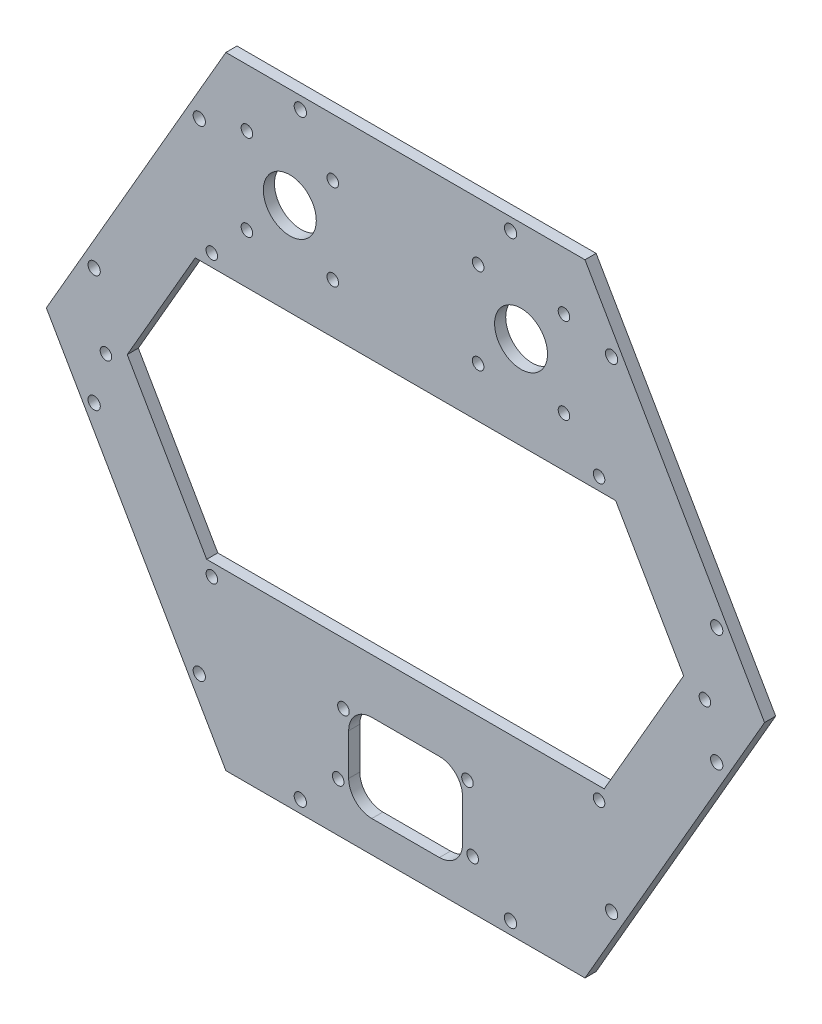
SolidWorks part; units mm, degrees
note: '?' marks a value the reader was unsure of. The reader was unsure of these and kept them because the rebuilt part matched: thickness of "Flange-base1", "Chapa metálica1", "Chapa metálica2", "Chapa metálica3", "Chapa metálica4", "Chapa metálica5", "Chapa metálica6", "Chapa metálica7", "Chapa metálica8".
ref_plane "Plano frontal" through (0, 0, 0) normal (0, 0, 1) x (1, 0, 0)
ref_plane "Plano superior" through (0, 0, 0) normal (0, 1, 0) x (1, 0, 0)
ref_plane "Plano direito" through (0, 0, 0) normal (1, 0, 0) x (0, 0, -1)
sketch "Esboço1" plane through (0, 0, 0) normal (0, 0, 1) x (1, 0, 0)
  line L0 (51.2514, 88.77) -> (102.5028, 0)
  line L5 (102.5028, 0) -> (51.2514, -88.77)
  line L6 (51.2514, -88.77) -> (-51.2514, -88.77)
  line L7 (-51.2514, -88.77) -> (-102.5028, 0)
  line L8 (-79.4088, 0) -> (-102.5028, 0) construction
  line L9 (79.4088, 0) -> (102.5028, 0) construction
  line L10 (-102.5028, 0) -> (-51.2514, 88.77)
  line L11 (-51.2514, 88.77) -> (51.2514, 88.77)
  line L12 (60, 33.617) -> (-60, 33.617)
  line L13 (-60, 33.617) -> (-79.4088, 0)
  line L14 (-79.4088, 0) -> (-56.7342, -39.2734)
  line L15 (-56.7342, -39.2734) -> (56.7342, -39.2734)
  line L16 (56.7342, -39.2734) -> (79.4088, 0)
  line L17 (79.4088, 0) -> (60, 33.617)
  line L18 (-51.2514, -88.77) -> (0, 0) construction
  line L19 (0, 0) -> (-102.5028, 0) construction
  line L20 (0, 0) -> (-51.2514, 88.77) construction
  line L21 (0, 0) -> (51.2514, 88.77) construction
  line L22 (0, 0) -> (102.5028, 0) construction
  line L23 (0, 0) -> (51.2514, -88.77) construction
  dimension "D1" = 102.5028
  dimension "D2" = 120
  dimension "D3" = 60
  dimension "D5" = 60
  dimension "D7" = 23.094
  dimension "D8" = 49.4966
base flange "Flange-base1" sketch "Esboço1" thickness 3.175 reverse thickness direction no parameters "D1"=0.7366
sketch "Esboço6" plane through (0, 0, 0) normal (0, 0, 1) x (1, 0, 0)
  line L0 (-16.2072, -73.17) -> (-16.2072, -61.37)
  line L1 (-9.6072, -54.77) -> (9.6928, -54.77)
  line L2 (16.2928, -61.37) -> (16.2928, -73.17)
  line L3 (9.6928, -79.77) -> (-9.6072, -79.77)
  line L4 (0, -88.77) -> (0, -54.77) construction
  line L5 (-51.2514, -88.77) -> (51.2514, -88.77) construction
  line L6 (-17.7, -56.67) -> (0, -56.67) construction
  line L7 (-19.2, -74.77) -> (0, -74.77) construction
  line L8 (0, -74.77) -> (19.2, -74.77) construction
  line L9 (0, -56.67) -> (17.7, -56.67) construction
  circle A2 centre (19.2, -74.77) radius 1.65
  circle A3 centre (17.7, -56.67) radius 1.65
  circle A4 centre (-17.7, -56.67) radius 1.65
  circle A5 centre (-19.2, -74.77) radius 1.65
  arc A8 (-9.6072, -79.77) -> (-16.2072, -73.17) centre (-9.6072, -73.17) cw
  arc A10 (-16.2072, -61.37) -> (-9.6072, -54.77) centre (-9.6072, -61.37) cw
  arc A12 (16.2928, -61.37) -> (9.6928, -54.77) centre (9.6928, -61.37) ccw
  arc A14 (9.6928, -79.77) -> (16.2928, -73.17) centre (9.6928, -73.17) ccw
  dimension "D8" = 6.6
  dimension "D1" = 25
  dimension "D2" = 32.5
  dimension "D3" = 17.7
  dimension "D4" = 19.2
  dimension "D5" = 18.1
  dimension "D6" = 9
  dimension "D7" = 5
extrude "Corte-extrusão1" cut sketch "Esboço6" against normal blind 10 contours L3 A14 L2 A12 L1 A10 L0 A8 | A4 | A3 | A2 | A5 normal cut yes
sketch "Esboço7" plane through (0, 0, 0) normal (0, 0, 1) x (1, 0, 0)
  line L0 (30, -85.27) -> (-30, -85.27) construction
  line L1 (-51.2514, -88.77) -> (51.2514, -88.77) construction
  line L2 (0, -85.27) -> (0, -88.77) construction
  circle A0 centre (-30, -85.27) radius 1.75
  circle A1 centre (30, -85.27) radius 1.75
  dimension "D2" = 60
  dimension "D3" = 3.5
  dimension "D1" = 3.5
extrude "Corte-extrusão2" cut sketch "Esboço7" against normal blind 10 normal cut yes
sketch "Esboço8" plane through (0, 0, 0) normal (0, 0, 1) x (1, 0, 0)
  circle A0 centre (-33, 60.0982) radius 7.555
  circle A1 centre (-20.75, 47.8482) radius 1.65
  dimension "D2" = 60.0982
  dimension "D3" = 15.1099
  dimension "D4" = 3.3
  dimension "D5" = 12.25
  dimension "D6" = 12.25
  dimension "D1" = 33
extrude "Corte-extrusão3" cut sketch "Esboço8" against normal blind 10 normal cut yes
pattern_circular "PadrãoCircular1" count 4 every 90 about axis through (-33, 60.0982, 0) along (0, 0, 1) of "Corte-extrusão3"
ref_axis "Eixo1" through (0, 0, -3.339) along (0, 0, 1)?
pattern_circular "PadrãoCircular2" count 6 over 360 about axis through (0, 0, 0) along (0, 0, 1) of "Corte-extrusão2"
mirror "Espelhar1" about plane through (0, 0, 0) normal (1, 0, 0) of "PadrãoCircular1", "Corte-extrusão3"
sketch "Esboço9" plane through (0, 0, 0) normal (0, 0, 1) x (1, 0, 0)
  circle A0 centre (-55.2577, 37.1718) radius 1.65
  circle A1 centre (-85.4808, -2.8282) radius 1.65
  circle A2 centre (85.4808, -2.8282) radius 1.65
  circle A3 centre (55.2577, 37.1718) radius 1.65
  circle A4 centre (55.2577, -42.8282) radius 1.65
  circle A5 centre (-55.2577, -42.8282) radius 1.65
  dimension "D1" = 3.3
extrude "Corte-extrusão4" cut sketch "Esboço9" against normal blind 10 normal cut yes
sketch "Esboço10" [suppressed] plane through (0, 0, 0) normal (0, 0, 1) x (1, 0, 0)
  line L0 (-51.2514, 88.77) -> (51.2514, 88.77)
  line L1 (51.2514, 88.77) -> (102.5028, 0)
  line L2 (102.5028, 0) -> (51.2514, -88.77)
  line L3 (51.2514, -88.77) -> (-51.2514, -88.77)
  line L4 (-51.2514, -88.77) -> (-102.5028, 0)
  line L5 (-102.5028, 0) -> (-51.2514, 88.77)
  line L6 (-127.0171, 0) -> (-63.5085, 110)
  line L7 (-63.5085, 110) -> (63.5085, 110)
  line L8 (63.5085, 110) -> (127.0171, 0)
  line L9 (127.0171, 0) -> (63.5085, -110)
  line L10 (63.5085, -110) -> (-63.5085, -110)
  line L11 (-63.5085, -110) -> (-127.0171, 0)
  line L12 (-102.5028, 0) -> (-127.0171, 0) construction
  line L13 (-51.2514, 88.77) -> (-63.5085, 110) construction
  line L14 (51.2514, -88.77) -> (63.5085, -110) construction
  line L15 (127.0171, 0) -> (102.5028, 0) construction
  line L16 (51.2514, 88.77) -> (63.5085, 110) construction
  line L17 (-51.2514, -88.77) -> (-63.5085, -110) construction
  line L18 (179.4678, 0) -> (-225.4204, 0) construction
  dimension "D1" = 220
extrude "Ressalto-extrusão1" [suppressed] add sketch "Esboço10" against normal blind 3.175 separate body
sketch "Curva-Linhas1" [suppressed] plane through (0, 0, 0) normal (0, 1, 0) x (1, 0, 0)
sketch "Caixa delimitadora1" [suppressed] plane through (0, 0, 0) normal (0, 1, 0) x (1, 0, 0)
sheet metal parameters "Chapa metálica1" thickness 3.175 parameters "D1"=0.7366, "D7"=3.18
flat pattern "Padrão-Plano1" [suppressed]
sketch "Curva-Linhas2" plane through (0, 0, 0) normal (0, 1, 0) x (1, 0, 0)
sketch3d "Caixa delimitadora2" [suppressed]
  line L0 (16.5481, -11.3149, 0) -> (-43.696, -11.3149, 0) construction
  line L1 (16.5481, 22.6297, 0) -> (-43.696, 22.6297, 0) construction
  line L2 (16.5481, -11.3149, 0) -> (16.5481, 22.6297, 0) construction
  line L3 (-43.696, -11.3149, 0) -> (-43.696, 22.6297, 0) construction
sheet metal parameters "Chapa metálica2" thickness 3.175 parameters "D1"=0.7366, "D7"=3.18
flat pattern "Padrão-Plano1"
sketch "Curva-Linhas2" plane through (0, 0, 0) normal (0, 1, 0) x (1, 0, 0)
sketch3d "Caixa delimitadora2" [suppressed]
  line L0 (-102.5028, -88.77, 0) -> (102.5028, -88.77, 0) construction
  line L1 (-102.5028, 88.77, 0) -> (102.5028, 88.77, 0) construction
  line L2 (-102.5028, -88.77, 0) -> (-102.5028, 88.77, 0) construction
  line L3 (102.5028, -88.77, 0) -> (102.5028, 88.77, 0) construction
sheet metal parameters "Chapa metálica3" thickness 3.175 parameters "D1"=0.7366, "D7"=3.18
flat pattern "Padrão-Plano1"
sketch "Curva-Linhas2" plane through (0, 0, 0) normal (0, 1, 0) x (1, 0, 0)
sketch3d "Caixa delimitadora2" [suppressed]
  line L0 (-102.5028, -88.77, 0) -> (102.5028, -88.77, 0) construction
  line L1 (-102.5028, 88.77, 0) -> (102.5028, 88.77, 0) construction
  line L2 (-102.5028, -88.77, 0) -> (-102.5028, 88.77, 0) construction
  line L3 (102.5028, -88.77, 0) -> (102.5028, 88.77, 0) construction
sheet metal parameters "Chapa metálica4" thickness 3.175 parameters "D1"=0.7366, "D7"=3.18
flat pattern "Padrão-Plano1"
sketch "Curva-Linhas2" plane through (0, 0, 0) normal (0, 1, 0) x (1, 0, 0)
sketch3d "Caixa delimitadora2" [suppressed]
  line L0 (-102.5028, -88.77, 0) -> (102.5028, -88.77, 0) construction
  line L1 (-102.5028, 88.77, 0) -> (102.5028, 88.77, 0) construction
  line L2 (-102.5028, -88.77, 0) -> (-102.5028, 88.77, 0) construction
  line L3 (102.5028, -88.77, 0) -> (102.5028, 88.77, 0) construction
sheet metal parameters "Chapa metálica5" thickness 3.175 parameters "D1"=0.7366, "D7"=3.18
flat pattern "Padrão-Plano1"
sketch "Curva-Linhas2" plane through (0, 0, 0) normal (0, 1, 0) x (1, 0, 0)
sketch3d "Caixa delimitadora2" [suppressed]
  line L0 (-102.5028, -88.77, 0) -> (102.5028, -88.77, 0) construction
  line L1 (-102.5028, 88.77, 0) -> (102.5028, 88.77, 0) construction
  line L2 (-102.5028, -88.77, 0) -> (-102.5028, 88.77, 0) construction
  line L3 (102.5028, -88.77, 0) -> (102.5028, 88.77, 0) construction
sheet metal parameters "Chapa metálica6" thickness 3.175 parameters "D1"=0.7366, "D7"=3.18
flat pattern "Padrão-Plano1"
sketch "Curva-Linhas2" plane through (0, 0, 0) normal (0, 1, 0) x (1, 0, 0)
sketch3d "Caixa delimitadora2" [suppressed]
  line L0 (-102.5028, -88.77, 0) -> (102.5028, -88.77, 0) construction
  line L1 (-102.5028, 88.77, 0) -> (102.5028, 88.77, 0) construction
  line L2 (-102.5028, -88.77, 0) -> (-102.5028, 88.77, 0) construction
  line L3 (102.5028, -88.77, 0) -> (102.5028, 88.77, 0) construction
sheet metal parameters "Chapa metálica7" thickness 3.175 parameters "D1"=0.7366, "D7"=3.18
flat pattern "Padrão-Plano1"
sketch "Curva-Linhas2" plane through (0, 0, 0) normal (0, 1, 0) x (1, 0, 0)
sketch3d "Caixa delimitadora2" [suppressed]
  line L0 (-102.5028, -88.77, 0) -> (102.5028, -88.77, 0) construction
  line L1 (-102.5028, 88.77, 0) -> (102.5028, 88.77, 0) construction
  line L2 (-102.5028, -88.77, 0) -> (-102.5028, 88.77, 0) construction
  line L3 (102.5028, -88.77, 0) -> (102.5028, 88.77, 0) construction
sheet metal parameters "Chapa metálica8" thickness 3.175 parameters "D1"=0.7366, "D7"=3.18
flat pattern "Padrão-Plano1"
sketch "Curva-Linhas2" plane through (0, 0, 0) normal (0, 1, 0) x (1, 0, 0)
sketch3d "Caixa delimitadora2" [suppressed]
  line L0 (-102.5028, -88.77, 0) -> (102.5028, -88.77, 0) construction
  line L1 (-102.5028, 88.77, 0) -> (102.5028, 88.77, 0) construction
  line L2 (-102.5028, -88.77, 0) -> (-102.5028, 88.77, 0) construction
  line L3 (102.5028, -88.77, 0) -> (102.5028, 88.77, 0) construction
